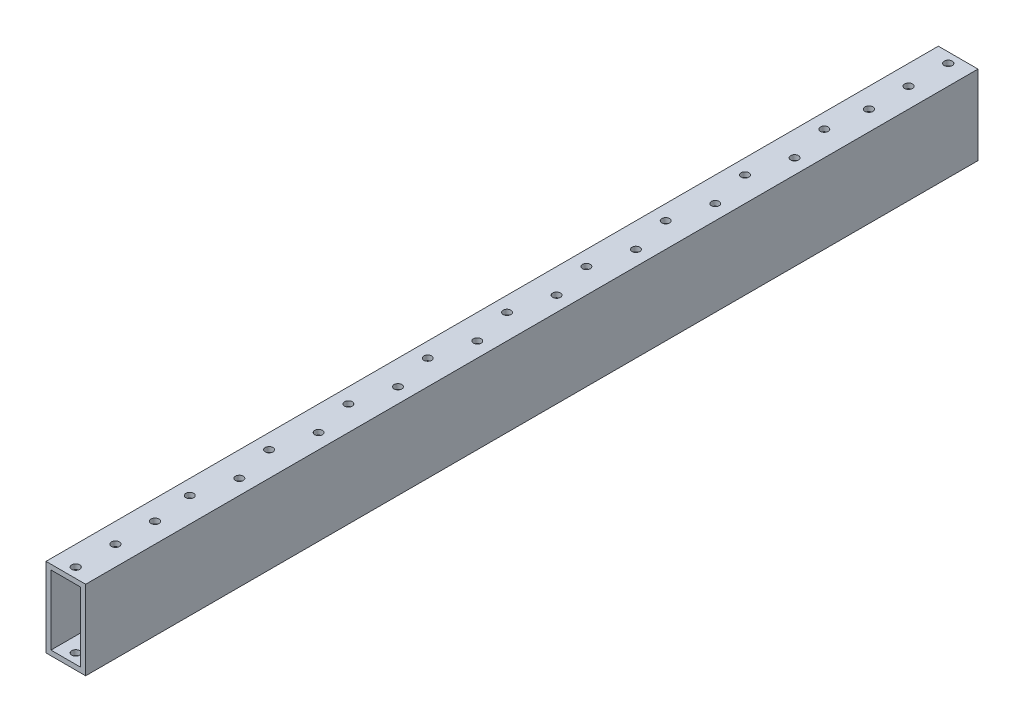
SolidWorks part; units mm, degrees
material "6061-T6 (SS)"
ref_plane "Front Plane" through (0, 0, 0) normal (0, 0, 1) x (1, 0, 0)
ref_plane "Top Plane" through (0, 0, 0) normal (0, 1, 0) x (1, 0, 0)
ref_plane "Right Plane" through (0, 0, 0) normal (1, 0, 0) x (0, 0, -1)
sketch "Sketch1" plane through (0, 0, 0) normal (0, 0, 1) x (1, 0, 0)
  line L1 (-12.7, -25.4) -> (12.7, -25.4)
  line L2 (-12.7, -25.4) -> (-12.7, 25.4)
  line L3 (-12.7, 25.4) -> (12.7, 25.4)
  line L4 (12.7, -25.4) -> (12.7, 25.4)
  line L5 (-12.7, -25.4) -> (12.7, 25.4) construction
  line L6 (-12.7, 25.4) -> (12.7, -25.4) construction
  point P0 (0, 0)
  point P5 (12.5935, 25.187)
  point P7 (-12.2185, -25.3425)
  point P8 (12.2383, -25.4)
  point P9 (6.35, 25.6515)
  point P10 (12.5294, -25.2819)
  point P12 (0, 0)
  point P13 (-12.7, -24.554)
  dimension "D1" = 50.8
  dimension "D2" = 25.4
extrude "Extrude-Thin1" add sketch "Sketch1" along normal blind 571.5 thin thin type one direction reverse wall 3.175
hole_wizard "#10 Clearance Hole1" positions "3DSketch1" profile "Sketch3" hole size "#10" standard "ANSI Inch" end condition through all
sketch3d "3DSketch1"
  line L1 (12.7, 25.4, 0) -> (-12.7, 25.4, 0) construction
  line L6 (0, 25.4, 571.5) -> (0, 25.4, 0) construction
  line L7 (12.7, 25.4, 571.5) -> (-12.7, 25.4, 571.5) construction
  point P57 (0, 25.4, 6.35)
  point P59 (0, 25.4, 31.75)
  point P61 (0, 25.4, 57.15)
  point P63 (0, 25.4, 539.75)
  point P65 (0, 25.4, 514.35)
  point P67 (0, 25.4, 565.15)
  dimension "D1" = 25.4
  dimension "D2" = 25.4
  dimension "D3" = 6.35
  dimension "D4" = 25.4
  dimension "D5" = 25.4
  dimension "D6" = 6.35
sketch "Sketch3" plane through (0, 25.4, 565.15) normal (1, 0, 0) x (0, 0, 1)
  line L0 (0, 0) -> (0, 50.8)
  line L1 (0, 50.8) -> (2.5527, 50.8)
  line L2 (2.5527, 50.8) -> (2.5527, 0)
  line L5 (2.5527, 0) -> (0, 0)
  line L11 (0, -6.35) -> (0, 107.95) construction
  dimension "Thru Hole Dia." = 5.1054
  dimension "Thru Hole Depth" = 50.8
hole_wizard "3/16 (0.195) Diameter Hole1" positions "Sketch4" profile "Sketch5" hole size "3/16" standard "ANSI Inch" end condition up to next
sketch "Sketch4" plane through (0, 25.4, 0) normal (0, 1, 0) x (1, 0, 0)
  point P145 (-3.1807, -82.55)
  point P148 (3.1693, -107.95)
  point P151 (-3.1807, -133.35)
  point P154 (3.1693, -158.75)
  point P157 (-3.1807, -184.15)
  point P160 (3.1693, -209.55)
  point P163 (-3.1807, -234.95)
  point P166 (3.1693, -260.35)
  point P169 (-3.1807, -285.75)
  point P172 (3.1693, -311.15)
  point P175 (-3.1807, -336.55)
  point P178 (3.1693, -361.95)
  point P181 (-3.1807, -387.35)
  point P184 (3.1693, -412.75)
  point P187 (-3.1807, -438.15)
  point P190 (3.1693, -463.55)
  point P193 (-3.1807, -488.95)
sketch "Sketch5" plane through (-3.1807, 25.4, 82.55) normal (1, 0, 0) x (0, 0, 1)
  line L0 (0, 0) -> (0, 3.175)
  line L1 (0, 3.175) -> (2.4765, 3.175)
  line L2 (2.4765, 3.175) -> (2.4765, 0)
  line L5 (2.4765, 0) -> (0, 0)
  line L11 (0, -6.35) -> (0, 107.95) construction
  dimension "Thru Hole Dia." = 4.953
  dimension "Thru Hole Depth" = 3.175
hole_wizard "3/16 (0.195) Diameter Hole2" positions "Sketch6" profile "Sketch7" hole size "3/16" standard "ANSI Inch"
sketch "Sketch6" plane through (0, -25.4, 0) normal (0, -1, 0) x (-1, 0, 0)
  point P23 (0.0807, -226.187)
  point P26 (0.0807, -251.587)
  point P29 (0.0807, -276.987)
  point P32 (0.0807, -302.387)
  point P35 (0.0807, -327.787)
  point P38 (0.0807, -353.187)
sketch "Sketch7" plane through (-0.0807, -25.4, 226.187) normal (1, 0, 0) x (0, 0, -1)
  line L0 (0, 0) -> (0, 4.663)
  line L1 (0, 4.663) -> (2.4765, 3.175)
  line L2 (2.4765, 3.175) -> (2.4765, 0)
  line L5 (2.4765, 0) -> (0, 0)
  line L10 (0, 4.663) -> (-2.4765, 3.175) construction
  line L11 (0, -6.35) -> (0, 107.95) construction
  dimension "Hole Dia." = 4.953
  dimension "Hole Depth" = 3.175
  dimension "Drill Angle" = 118
